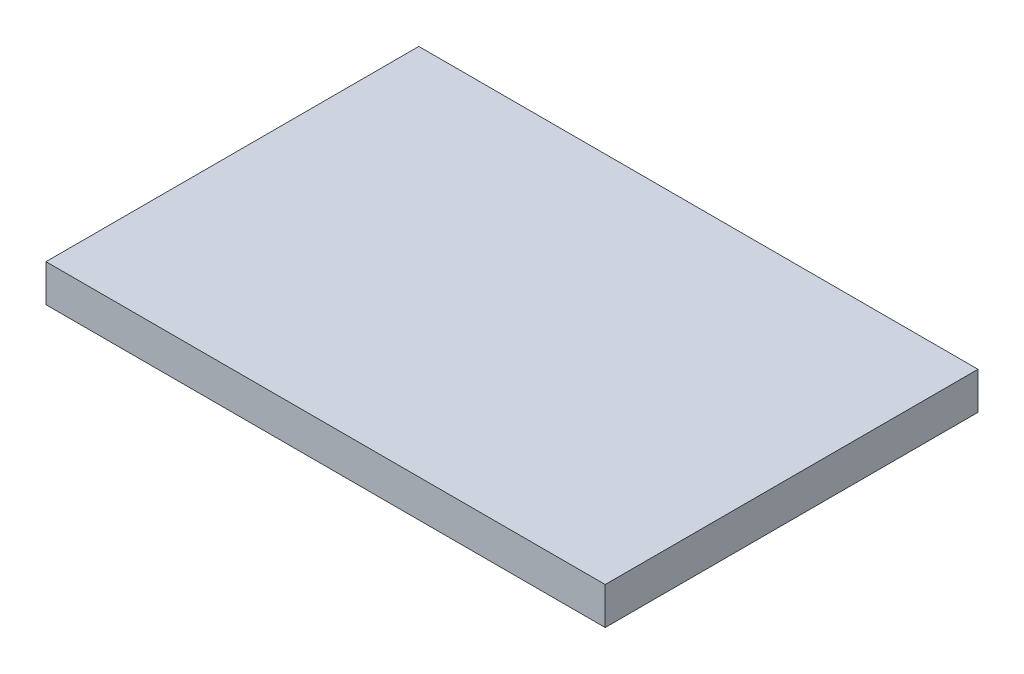
SolidWorks part; units mm, degrees
ref_plane "Front Plane" through (0, 0, 0) normal (0, 0, 1) x (1, 0, 0)
ref_plane "Top Plane" through (0, 0, 0) normal (0, 1, 0) x (1, 0, 0)
ref_plane "Right Plane" through (0, 0, 0) normal (1, 0, 0) x (0, 0, -1)
sketch "Sketch1" plane through (0, 0, 0) normal (0, 1, 0) x (1, 0, 0)
  line L1 (-150, -100) -> (150, -100)
  line L2 (-150, -100) -> (-150, 100)
  line L3 (-150, 100) -> (150, 100)
  line L4 (150, -100) -> (150, 100)
  line L5 (-150, -100) -> (150, 100) construction
  line L6 (-150, 100) -> (150, -100) construction
  point P0 (0, 0)
  dimension "D1" = 300
  dimension "D2" = 200
extrude "Boss-Extrude1" add sketch "Sketch1" along normal mid plane 20
